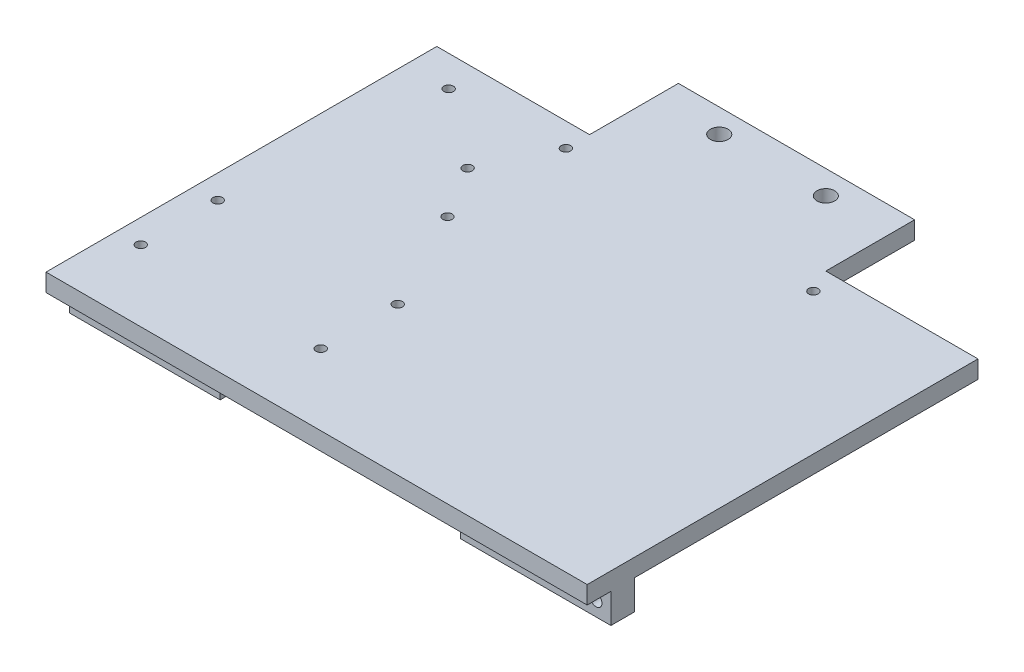
SolidWorks part; units mm, degrees
ref_plane "Front Plane" through (0, 0, 0) normal (0, 0, 1) x (1, 0, 0)
ref_plane "Top Plane" through (0, 0, 0) normal (0, 1, 0) x (1, 0, 0)
ref_plane "Right Plane" through (0, 0, 0) normal (1, 0, 0) x (0, 0, -1)
sketch "Sketch1" plane through (0, 0, 0) normal (0, 1, 0) x (1, 0, 0)
  line L1 (0, 0) -> (116.078, 0)
  line L2 (0, 0) -> (0, 102.87)
  line L3 (0, 102.87) -> (116.078, 102.87)
  line L4 (116.078, 0) -> (116.078, 102.87)
  dimension "D1" = 102.87
  dimension "D2" = 116.078
extrude "Boss-Extrude1" add sketch "Sketch1" along normal blind 3.81
sketch "Sketch2" plane through (0, 3.81, 0) normal (0, 1, 0) x (1, 0, 0)
  line L0 (116.078, 102.87) -> (0, 102.87) construction
  line L1 (0, 102.87) -> (32.766, 102.87)
  line L2 (0, 102.87) -> (0, 83.82)
  line L3 (0, 83.82) -> (32.766, 83.82)
  line L4 (32.766, 102.87) -> (32.766, 83.82)
  line L5 (116.078, 102.87) -> (83.439, 102.87)
  line L6 (116.078, 102.87) -> (116.078, 83.82)
  line L7 (116.078, 83.82) -> (83.439, 83.82)
  line L8 (83.439, 102.87) -> (83.439, 83.82)
  circle A0 centre (46.609, 97.79) radius 1.905
  circle A1 centre (69.469, 97.79) radius 1.905
  point P14 (58.039, 102.87)
  point P17 (58.039, 102.87)
  dimension "D5" = 11.43
  dimension "D8" = 3.81
  dimension "D10" = 3.81
  dimension "D1" = 19.05
  dimension "D2" = 19.05
  dimension "D3" = 32.639
  dimension "D4" = 32.766
  dimension "D6" = 11.43
  dimension "D7" = 5.08
  dimension "D9" = 5.08
extrude "Cut-Extrude1" cut sketch "Sketch2" against normal up to surface (3.81 mm away) up to face at (58.039, 0, -51.435)
sketch "Sketch3" plane through (0, 0, 0) normal (0, -1, 0) x (1, 0, 0)
  line L0 (0, -83.82) -> (0, 0) construction
  line L1 (0, -5.08) -> (32.258, -5.08)
  line L2 (0, -5.08) -> (0, -10.16)
  line L3 (0, -10.16) -> (32.258, -10.16)
  line L4 (32.258, -5.08) -> (32.258, -10.16)
  line L5 (116.078, 0) -> (116.078, -83.82) construction
  line L6 (116.078, -5.08) -> (83.82, -5.08)
  line L7 (116.078, -5.08) -> (116.078, -10.16)
  line L8 (116.078, -10.16) -> (83.82, -10.16)
  line L9 (83.82, -5.08) -> (83.82, -10.16)
  line L10 (0, 0) -> (116.078, 0) construction
  dimension "D1" = 5.08
  dimension "D2" = 5.08
  dimension "D3" = 32.258
extrude "Boss-Extrude2" add sketch "Sketch3" along normal blind 6.35
sketch "Sketch4" plane through (0, 0, -5.08) normal (0, 0, 1) x (1, 0, 0)
  line L0 (0, -6.35) -> (0, 0) construction
  line L1 (32.258, -6.35) -> (0, -6.35) construction
  line L2 (116.078, -6.35) -> (116.078, 0) construction
  circle A0 centre (3.175, -3.175) radius 1.27
  circle A1 centre (11.811, -3.175) radius 1.27
  circle A2 centre (20.447, -3.175) radius 1.27
  circle A3 centre (29.083, -3.175) radius 1.27
  circle A4 centre (86.995, -3.175) radius 1.27
  circle A5 centre (95.631, -3.175) radius 1.27
  circle A6 centre (104.267, -3.175) radius 1.27
  circle A7 centre (112.903, -3.175) radius 1.27
  dimension "D1" = 2.54
  dimension "D2" = 8.636
  dimension "D3" = 8.636
  dimension "D4" = 8.636
  dimension "D5" = 3.175
  dimension "D6" = 3.175
  dimension "D7" = 3.175
  dimension "D8" = 8.636
  dimension "D9" = 8.636
  dimension "D10" = 8.636
extrude "Cut-Extrude2" cut sketch "Sketch4" against normal up to surface (5.08 mm away) up to face at (12.0968, -3.9688, -10.16)
sketch "Sketch5" plane through (0, 3.81, 0) normal (0, 1, 0) x (1, 0, 0)
  line L0 (0, 83.82) -> (32.766, 83.82) construction
  line L1 (0, 83.82) -> (0, 0) construction
  line L3 (0, 10.16) -> (32.258, 10.16) construction
  circle A0 centre (25.908, 64.516) radius 1.016
  circle A1 centre (9.144, 77.216) radius 1.016
  circle A2 centre (32.766, 78.74) radius 1.016
  circle A3 centre (85.852, 78.74) radius 1.016
  circle A4 centre (32.766, 53.34) radius 1.016
  circle A5 centre (5.08, 31.75) radius 1.016
  circle A6 centre (43.688, 31.75) radius 1.016
  circle A7 centre (5.08, 15.24) radius 1.016
  circle A8 centre (43.688, 15.24) radius 1.016
  dimension "D1" = 6.604
  dimension "D2" = 9.144
  dimension "D4" = 25.908
  dimension "D5" = 2.032
  dimension "D6" = 25.4
  dimension "D7" = 53.086
  dimension "D8" = 2.032
  dimension "D9" = 0
  dimension "D13" = 2.032
  dimension "D14" = 5.08
  dimension "D15" = 5.08
  dimension "D3" = 19.304
  dimension "D10" = 5.08
  dimension "D11" = 38.608
  dimension "D12" = 16.51
extrude "Cut-Extrude4" cut sketch "Sketch5" against normal up to surface (3.81 mm away) up to face at (46.609, 0, -99.695)
